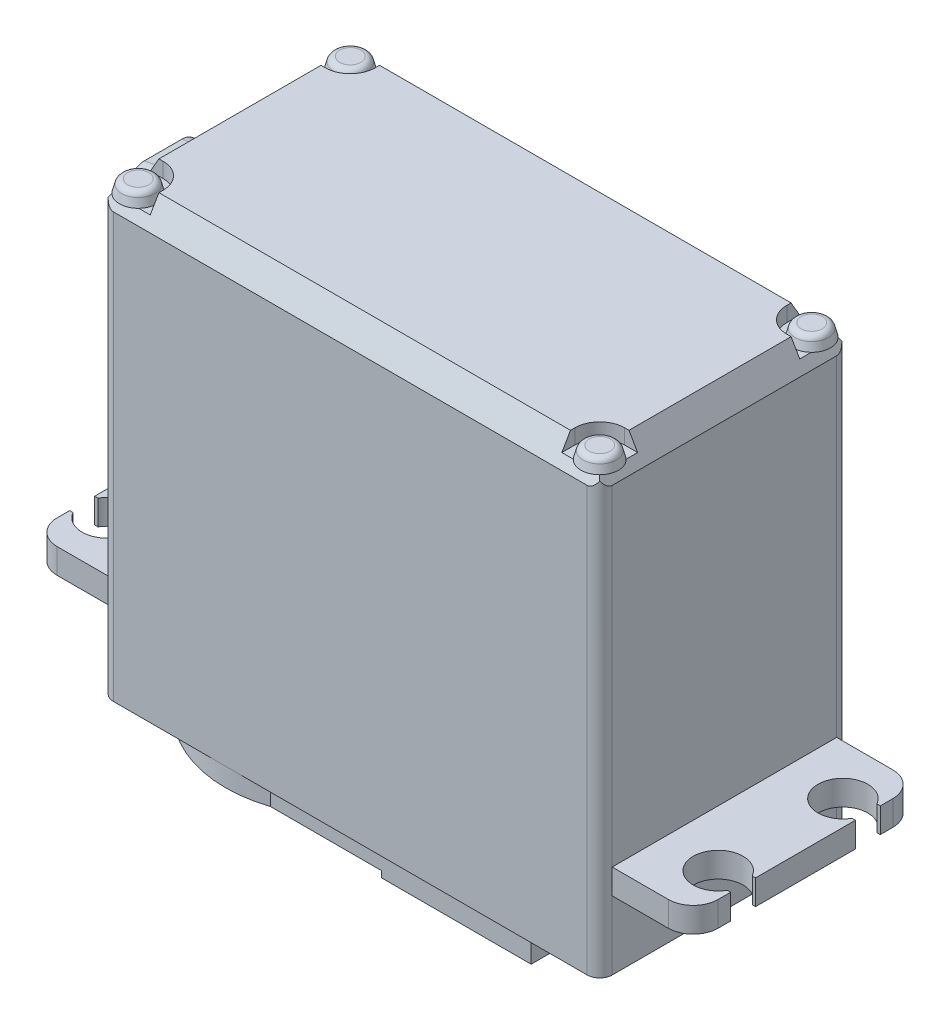
SolidWorks part; units mm, degrees
ref_plane "前视基准面" through (0, 0, 0) normal (0, 0, 1) x (1, 0, 0)
ref_plane "上视基准面" through (0, 0, 0) normal (0, 1, 0) x (1, 0, 0)
ref_plane "右视基准面" through (0, 0, 0) normal (1, 0, 0) x (0, 0, -1)
sketch "草图1" plane through (0, 0, 0) normal (0, 1, 0) x (1, 0, 0)
  line L1 (0, 0) -> (40, 0)
  line L2 (0, 0) -> (0, -20)
  line L3 (0, -20) -> (40, -20)
  line L4 (40, 0) -> (40, -20)
  point P4 (0, 0)
  dimension "D1" = 40
  dimension "D2" = 20
extrude "凸台-拉伸1" add sketch "草图1" along normal blind 28.5
sketch "草图3" plane through (0, 0, 0) normal (0, 1, 0) x (1, 0, 0)
  line L0 (0, 0) -> (0, -20) construction
  line L7 (-6.5, -1) -> (46.5, -1)
  line L8 (-6.5, -1) -> (-6.5, -19)
  line L9 (-6.5, -19) -> (46.5, -19)
  line L10 (46.5, -1) -> (46.5, -19)
  line L11 (-6.5, -10) -> (0, -10) construction
  line L12 (20, -1) -> (20, 0) construction
  line L13 (40, 0) -> (0, 0) construction
  line L14 (40, 0) -> (0, 0) construction
  point P2 (0, 0)
  point P15 (0, 0)
  dimension "D1" = 18
  dimension "D2" = 53
sketch "草图8" plane through (0, 0, 0) normal (0, 1, 0) x (1, 0, 0)
  line L0 (0, -10) -> (-4.5, -10) construction
  line L1 (0, 0) -> (0, -20) construction
  line L2 (0, -10) -> (40, -10) construction
  line L3 (40, -20) -> (40, 0) construction
  line L4 (40, -10) -> (44.5, -10) construction
  line L5 (44.5, -10) -> (44.5, -5) construction
  line L6 (44.5, -10) -> (44.5, -15) construction
  line L7 (-4.5, -10) -> (-4.5, -5) construction
  line L8 (-4.5, -10) -> (-4.5, -15) construction
  line L9 (-4.5, -5) -> (-9.5, -5) construction
  line L10 (-4.5, -15) -> (-9.5, -15) construction
  line L11 (-9.5, -5) -> (-9.5, -4) construction
  line L12 (-9.5, -5) -> (-9.5, -6) construction
  line L13 (-9.5, -15) -> (-9.5, -14) construction
  line L14 (-9.5, -15) -> (-9.5, -16) construction
  line L15 (44.5, -5) -> (49.5, -5) construction
  line L16 (49.5, -5) -> (49.5, -4) construction
  line L17 (49.5, -5) -> (49.5, -6) construction
  line L18 (44.5, -15) -> (49.5, -15) construction
  line L19 (49.5, -15) -> (49.5, -14) construction
  line L20 (49.5, -15) -> (49.5, -16) construction
  line L21 (-9.5, -6) -> (-6.2321, -6)
  line L22 (-9.5, -4) -> (-6.2321, -4)
  line L23 (-9.5, -14) -> (-6.2321, -14)
  line L24 (-9.5, -16) -> (-6.2321, -16)
  line L25 (49.5, -4) -> (46.2321, -4)
  line L26 (49.5, -6) -> (46.2321, -6)
  line L27 (49.5, -14) -> (46.2321, -14)
  line L28 (49.5, -16) -> (46.2321, -16)
  line L29 (49.5, -4) -> (49.5, -6)
  line L30 (49.5, -14) -> (49.5, -16)
  line L31 (-9.5, -4) -> (-9.5, -6)
  line L32 (-9.5, -14) -> (-9.5, -16)
  circle A0 centre (-4.5, -5) radius 2 construction
  circle A1 centre (-4.5, -15) radius 2 construction
  circle A2 centre (44.5, -5) radius 2 construction
  circle A3 centre (44.5, -15) radius 2 construction
  arc A4 (-6.2321, -4) -> (-6.2352, -5.9945) centre (-4.5, -5) cw
  arc A5 (-6.2321, -14) -> (-6.2598, -15.9504) centre (-4.5, -15) cw
  arc A6 (46.2321, -4) -> (46.2321, -6) centre (44.5, -5) ccw
  arc A7 (46.2321, -14) -> (46.2321, -16) centre (44.5, -15) ccw
  dimension "D2" = 4
  dimension "D3" = 4
  dimension "D4" = 4
  dimension "D5" = 4
  dimension "D1" = 49
  dimension "D6" = 10
  dimension "D7" = 10
  dimension "D8" = 1
  dimension "D9" = 1
  dimension "D10" = 1
  dimension "D11" = 1
  dimension "D12" = 1
  dimension "D13" = 1
  dimension "D14" = 1
  dimension "D15" = 1
  dimension "D16" = 5
  dimension "D17" = 5
  dimension "D18" = 5
  dimension "D19" = 5
sketch "草图7" plane through (0, 0, 0) normal (0, 1, 0) x (1, 0, 0)
  line L0 (0, -10) -> (10, -10)
  line L1 (0, 0) -> (0, -20) construction
  circle A0 centre (10, -10) radius 2.5
  dimension "D2" = 5
  dimension "D1" = 10
extrude "凸台-拉伸4" add sketch "草图7" against normal blind 6.9754 contours A0
extrude "凸台-拉伸5" add sketch "草图1<2>" against normal blind 7.5
sketch "草图1<2>" plane through (0, 0, 0) normal (0, 1, 0) x (1, 0, 0) same geometry as "草图1"
extrude "凸台-拉伸6" add sketch "草图3" against normal blind 2
extrude "切除-拉伸4" cut sketch "草图8" against normal mid plane 10 contours L25 A6 L26 L29 | L27 A7 L28 L30 | A4 L22 L31 L21 | A5 L23 L32 L24 region at (-5.6384, 0, 5) region at (-5.6384, 0, 15) region at (45.6384, 0, 5) region at (45.6384, 0, 15)
sketch "草图9" plane through (0, -7.5, 0) normal (0, -1, 0) x (1, 0, 0)
  line L0 (40, 10) -> (34, 10) construction
  line L1 (40, 20) -> (40, 0) construction
  line L2 (34, 19.5) -> (34, 0.5)
  line L3 (0, 20) -> (40, 20) construction
  line L4 (40, 0) -> (0, 0) construction
  line L5 (34, 19.5) -> (13.1225, 19.5)
  line L6 (34, 0.5) -> (13.1225, 0.5)
  line L7 (0, 0) -> (0, 20) construction
  circle A0 centre (10, 10) radius 10 construction
  arc A1 (13.1225, 19.5) -> (13.1225, 0.5) centre (10, 10) ccw
  dimension "D6" = 20
  dimension "D1" = 6
  dimension "D2" = 20
  dimension "D3" = 19
  dimension "D4" = 10
  dimension "D5" = 10
extrude "凸台-拉伸7" add sketch "草图9" along normal blind 1.5 contours A1 L6 L2 L5 region at (17.8154, -7.5, 10)
sketch "草图13" plane through (0, -7.5, 0) normal (0, -1, 0) x (1, 0, 0)
  line L0 (34, 0.5) -> (13.1225, 0.5) construction
  line L1 (34, 19.5) -> (22, 19.5)
  line L2 (34, 19.5) -> (34, 0.5)
  line L3 (34, 0.5) -> (22, 0.5)
  line L4 (22, 19.5) -> (22, 0.5)
  dimension "D1" = 12
extrude "凸台-拉伸8" add sketch "草图13" along normal blind 2
sketch "草图14" plane through (0, -7.5, 0) normal (0, -1, 0) x (1, 0, 0)
  line L0 (40, 19) -> (40, 1) construction
  line L1 (31, 10) -> (40, 10) construction
  line L2 (40, 20) -> (40, 0) construction
  circle A0 centre (31, 10) radius 6
  dimension "D2" = 12
  dimension "D1" = 9
extrude "凸台-拉伸9" add sketch "草图14" along normal blind 1.5 contours A0
ref_plane "基准面2" through (0, 0, 10) normal (0, 0, -1) x (-1, 0, 0)
sketch "草图15" plane through (0, 0, 10) normal (0, 0, -1) x (-1, 0, 0)
  line L1 (0, 28.5) -> (0, -7.5) construction
  line L2 (0, -3.2) -> (-40, -3.2)
  line L3 (-40, 28.5) -> (-40, -7.5) construction
  line L5 (-40, -3.2) -> (-46.5, -2)
  line L6 (-46.5, -2) -> (6.5, -2)
  line L7 (6.5, -2) -> (0, -3.2)
  dimension "D1" = 1.2
extrude "凸台-拉伸10" add sketch "草图15" along normal mid plane 0.5
sketch "草图16" plane through (0, 0, 0) normal (0, 0, 1) x (1, 0, 0)
  line L0 (0, 26.5) -> (1.1547, 28.5)
  line L1 (0, 28.5) -> (0, -7.5) construction
  line L2 (0, 28.5) -> (40, 28.5) construction
  line L3 (1.1547, 28.5) -> (38.8453, 28.5)
  line L4 (38.8453, 28.5) -> (40, 26.5)
  line L5 (40, 28.5) -> (40, -7.5) construction
  line L6 (40, 26.5) -> (45, 26.5)
  line L7 (45, 26.5) -> (45, 36.5)
  line L8 (45, 36.5) -> (-5, 36.5)
  line L9 (-5, 36.5) -> (-5, 26.5)
  line L10 (-5, 26.5) -> (0, 26.5)
  point P6 (-14.9929, 45.5019)
  dimension "D1" = 10
  dimension "D2" = 50
  dimension "D3" = 120
  dimension "D4" = 2
  dimension "D5" = 2
  dimension "D6" = 120
extrude "切除-拉伸5" cut sketch "草图16" against normal mid plane 100 contours L9 L10 L0 L3 L4 L6 L7 L8
sketch "草图18" plane through (0, 0, 0) normal (1, 0, 0) x (0, 0, -1)
  line L0 (-20, 26.5) -> (-18.8453, 28.5)
  line L1 (0, 28.5) -> (-20, 28.5) construction
  line L2 (-18.8453, 28.5) -> (-1.1547, 28.5)
  line L3 (-1.1547, 28.5) -> (0, 26.5)
  line L4 (0, 26.5) -> (15, 26.5)
  line L5 (15, 26.5) -> (15, 36.5)
  line L6 (15, 36.5) -> (-35, 36.5)
  line L7 (-35, 36.5) -> (-35, 26.5)
  line L8 (-35, 26.5) -> (-20, 26.5)
  dimension "D1" = 120
  dimension "D2" = 120
  dimension "D3" = 50
  dimension "D4" = 10
extrude "切除-拉伸6" cut sketch "草图18" against normal mid plane 100 contours L6 L7 L8 L0 L2 L3 L4 L5
sketch "草图22" plane through (0, 28.5, 0) normal (0, 1, 0) x (1, 0, 0)
  line L0 (0, 0) -> (0, -1.5)
  line L1 (0, -1) -> (0, -19) construction
  line L2 (0, -1.5) -> (1.5, -1.5)
  line L3 (3.5, -1.5) -> (3.5, 0.5)
  line L4 (3.5, 0.5) -> (-0.5, 0.5)
  line L5 (1.5, -3.5) -> (-0.5, -3.5)
  line L6 (-0.5, -3.5) -> (-0.5, 0.5)
  line L7 (19.8, -10) -> (-19.8, -10) construction
  line L8 (3.5, -18.5) -> (3.5, -20.5)
  line L9 (1.5, -16.5) -> (-0.5, -16.5)
  line L10 (-0.5, -16.5) -> (-0.5, -20.5)
  line L11 (3.5, -20.5) -> (-0.5, -20.5)
  line L12 (20, -1.1547) -> (20, -18.8453) construction
  line L13 (1.1547, -1.1547) -> (38.8453, -1.1547) construction
  line L14 (1.1547, -18.8453) -> (38.8453, -18.8453) construction
  line L15 (36.5, -18.5) -> (36.5, -20.5)
  line L16 (36.5, -20.5) -> (40.5, -20.5)
  line L17 (40.5, -16.5) -> (40.5, -20.5)
  line L18 (38.5, -16.5) -> (40.5, -16.5)
  line L19 (36.5, -1.5) -> (36.5, 0.5)
  line L20 (38.5, -3.5) -> (40.5, -3.5)
  line L21 (40.5, -3.5) -> (40.5, 0.5)
  line L22 (36.5, 0.5) -> (40.5, 0.5)
  circle A0 centre (1.5, -1.5) radius 2 construction
  arc A1 (3.5, -1.5) -> (1.3994, -3.4975) centre (1.5, -1.5) cw
  arc A2 (3.5, -18.5) -> (1.3994, -16.5025) centre (1.5, -18.5) ccw
  arc A3 (36.5, -18.5) -> (38.6006, -16.5025) centre (38.5, -18.5) cw
  arc A4 (36.5, -1.5) -> (38.6006, -3.4975) centre (38.5, -1.5) ccw
  point P13 (0.5, -3.5)
  point P20 (0.5, -16.5)
  line M8 (38.8453, -1.1547) -> (1.1547, -1.1547)
  line M9 (1.1547, -1.1547) -> (1.1547, -18.8453)
  line M10 (1.1547, -18.8453) -> (38.8453, -18.8453)
  line M11 (38.8453, -18.8453) -> (38.8453, -1.1547)
  dimension "D3" = 4
  dimension "D1" = 1.5
  dimension "D2" = 1.5
  dimension "D4" = 4
extrude "切除-拉伸11" cut sketch "草图22" against normal blind 1.2 contours L8 A2 L9 M9 M10 | A1 L3 L5 M8 M9 | L19 A4 L20 M11 M8 | A3 L15 L18 M10 M11 | L18 L15 L16 L17 M11 M10 | L22 L19 L20 L21 M8 M11 | L6 L5 L3 L4 | L11 L8 L9 L10 M10 M9 region at (2.1931, 28.5, 2.1931) region at (1.0666, 28.5, 1.0666) region at (37.8069, 28.5, 2.1931) region at (38.9334, 28.5, 1.0666) region at (1.0666, 28.5, 18.9334) region at (2.1931, 28.5, 17.8069) region at (37.8069, 28.5, 17.8069) region at (38.9334, 28.5, 18.9334)
sketch "草图24" plane through (0, 28.5, 0) normal (0, 1, 0) x (1, 0, 0)
  line L0 (0, 0) -> (1.5, 0)
  line L1 (0, 0) -> (40, 0) construction
  line L2 (1.5, 0) -> (1.5, -1.5)
  line L3 (40, 0) -> (38.5, 0)
  line L4 (38.5, 0) -> (38.5, -1.5)
  line L5 (40, -20) -> (38.5, -20)
  line L6 (0, -20) -> (40, -20) construction
  line L7 (38.5, -20) -> (38.5, -18.5)
  line L8 (0, -20) -> (1.5, -20)
  line L9 (1.5, -20) -> (1.5, -18.5)
  circle A0 centre (1.5, -1.5) radius 1.5
  circle A1 centre (38.5, -1.5) radius 1.5
  circle A2 centre (38.5, -18.5) radius 1.5
  circle A3 centre (1.5, -18.5) radius 1.5
  dimension "D1" = 1.5
  dimension "D2" = 1.5
  dimension "D3" = 1.5
  dimension "D4" = 1.5
  dimension "D5" = 1.5
  dimension "D6" = 1.5
  dimension "D7" = 1.5
  dimension "D8" = 1.5
sketch "草图25" plane through (0, 27.3, 0) normal (0, 1, 0) x (1, 0, 0)
  circle A0 centre (1.5, -1.5) radius 1.5
  circle A1 centre (38.5, -1.5) radius 1.5
  circle A2 centre (38.5, -18.5) radius 1.5
  circle A3 centre (1.5, -18.5) radius 1.5
extrude "凸台-拉伸12" add sketch "草图25" along normal blind 1 draft 15
sketch "草图29" plane through (0, -9, 0) normal (0, -1, 0) x (1, 0, 0)
  circle A0 centre (10, 10) radius 6.25
  dimension "D1" = 12.5
extrude "凸台-拉伸15" add sketch "草图29" along normal blind 1.2
sketch "草图30" plane through (0, -10.2, 0) normal (0, -1, 0) x (1, 0, 0)
  circle A0 centre (10, 10) radius 5
  dimension "D1" = 10
extrude "凸台-拉伸16" add sketch "草图30" along normal blind 0.3
sketch "草图31" plane through (0, -10.5, 0) normal (0, -1, 0) x (1, 0, 0)
  line L0 (10, 10) -> (13, 10) construction
  line L1 (10, 10) -> (12.9763, 10.376) construction
  line L2 (10, 10) -> (12.9057, 10.7461) construction
  line L3 (12.9763, 10.376) -> (12.4215, 10.6217)
  line L4 (12.9763, 10.376) -> (12.5, 10)
  line L5 (12.9763, 9.624) -> (12.5, 10)
  line L6 (12.9763, 9.624) -> (12.4215, 9.3783)
  line L7 (12.7893, 8.8956) -> (12.4215, 9.3783)
  line L8 (12.7893, 8.8956) -> (12.1908, 8.7956)
  line L9 (12.4271, 8.2366) -> (12.1908, 8.7956)
  line L10 (12.4271, 8.2366) -> (11.8224, 8.2886)
  line L11 (11.9123, 7.6885) -> (11.8224, 8.2886)
  line L12 (11.9123, 7.6885) -> (11.3396, 7.8892)
  line L13 (11.2773, 7.2855) -> (11.3396, 7.8892)
  line L14 (11.2773, 7.2855) -> (10.7725, 7.6224)
  line L15 (10.5621, 7.0531) -> (10.7725, 7.6224)
  line L16 (10.5621, 7.0531) -> (10.157, 7.5049)
  line L17 (9.8116, 7.0059) -> (10.157, 7.5049)
  line L18 (9.8116, 7.0059) -> (9.5315, 7.5443)
  line L19 (9.0729, 7.1468) -> (9.5315, 7.5443)
  line L20 (9.0729, 7.1468) -> (8.9356, 7.7379)
  line L21 (8.3925, 7.467) -> (8.9356, 7.7379)
  line L22 (8.3925, 7.467) -> (8.4064, 8.0737)
  line L23 (7.8131, 7.9464) -> (8.4064, 8.0737)
  line L24 (7.8131, 7.9464) -> (7.9775, 8.5305)
  line L25 (7.3711, 8.5547) -> (7.9775, 8.5305)
  line L26 (7.3711, 8.5547) -> (7.6756, 9.0797)
  line L27 (7.0943, 9.2539) -> (7.6756, 9.0797)
  line L28 (7.0943, 9.2539) -> (7.5197, 9.6867)
  line L29 (7, 10) -> (7.5197, 9.6867)
  line L30 (7, 10) -> (7.5197, 10.3133)
  line L31 (7.0943, 10.7461) -> (7.5197, 10.3133)
  line L32 (7.0943, 10.7461) -> (7.6756, 10.9203)
  line L33 (7.3711, 11.4453) -> (7.6756, 10.9203)
  line L34 (7.3711, 11.4453) -> (7.9775, 11.4695)
  line L35 (7.8131, 12.0536) -> (7.9775, 11.4695)
  line L36 (7.8131, 12.0536) -> (8.4064, 11.9263)
  line L37 (8.3925, 12.533) -> (8.4064, 11.9263)
  line L38 (8.3925, 12.533) -> (8.9356, 12.2621)
  line L39 (9.0729, 12.8532) -> (8.9356, 12.2621)
  line L40 (9.0729, 12.8532) -> (9.5315, 12.4557)
  line L41 (9.8116, 12.9941) -> (9.5315, 12.4557)
  line L42 (9.8116, 12.9941) -> (10.157, 12.4951)
  line L43 (10.5621, 12.9469) -> (10.157, 12.4951)
  line L44 (10.5621, 12.9469) -> (10.7725, 12.3776)
  line L45 (11.2773, 12.7145) -> (10.7725, 12.3776)
  line L46 (11.2773, 12.7145) -> (11.3396, 12.1108)
  line L47 (11.9123, 12.3115) -> (11.3396, 12.1108)
  line L48 (11.9123, 12.3115) -> (11.8224, 11.7114)
  line L49 (12.4271, 11.7634) -> (11.8224, 11.7114)
  line L50 (12.4271, 11.7634) -> (12.1908, 11.2044)
  line L51 (12.7893, 11.1044) -> (12.1908, 11.2044)
  line L52 (12.7893, 11.1044) -> (12.4215, 10.6217)
  circle A0 centre (10, 10) radius 3 construction
  circle A1 centre (10, 10) radius 2.5 construction
  point P83 (10, 10)
  dimension "D1" = 5
  dimension "D2" = 6
  dimension "D5" = 0.5
  dimension "D3" = 7.2
  dimension "D4" = 7.2
  dimension "D6" = 25
extrude "凸台-拉伸17" add sketch "草图31" along normal blind 3.5
sketch "草图33" plane through (0, -10.5, 0) normal (0, -1, 0) x (1, 0, 0)
  circle A0 centre (10, 10) radius 1.25
  dimension "D1" = 2.5
extrude "切除-拉伸12" cut sketch "草图33" along normal blind 10 contours A0
fillet "圆角1" radius 2 4 edges at (46.5, -1, 19) (46.5, -1, 1) (-6.5, -1, 1) (-6.5, -1, 19)
fillet "圆角2" radius 1 4 edges at (0, 9.5, 20) (40, 9.5, 20) (40, 9.5, 0) (0, 9.5, 0)
fillet "圆角4" radius 0.5 4 edges at (38.5, 28.3, 2.7321) (1.5, 28.3, 2.7321) (1.5, 28.3, 19.7321) (38.5, 28.3, 19.7321)
sketch "草图34" plane through (0, 0, 0) normal (-1, 0, 0) x (0, 0, 1)
  line L0 (10, 28.5) -> (10, 21.5) construction
  line L1 (16.5, 28.5) -> (3.5, 28.5) construction
  line L2 (10, 18.7) -> (10, -18.7) construction
  line L3 (10, 21.5) -> (6.5, 21.5) construction
  line L4 (6.5, 23.75) -> (13.5, 23.75)
  line L5 (6.5, 23.75) -> (6.5, 19.25)
  line L6 (6.5, 19.25) -> (13.5, 19.25)
  line L7 (13.5, 23.75) -> (13.5, 19.25)
  point P12 (10, 23.75)
  dimension "D1" = 7
  dimension "D2" = 7
  dimension "D3" = 4.5
extrude "凸台-拉伸18" add sketch "草图34" along normal blind 1 contours L4 L7 L6 L5
sketch "草图35" plane through (-1, 0, 0) normal (-1, 0, 0) x (0, 0, 1)
  line L0 (10, 23.5) -> (10, 21.5) construction
  line L1 (10, 18.7) -> (10, -18.7) construction
  line L2 (10, 21.5) -> (10, 19.5) construction
  line L3 (10, 21.5) -> (13.5, 21.5) construction
  line L4 (13.5, 23.75) -> (13.5, 19.25) construction
  line L5 (8.5, 23.5) -> (11.5, 23.5)
  line L6 (8.5, 19.5) -> (11.5, 19.5)
  circle A0 centre (11.5, 21.5) radius 2 construction
  arc A1 (11.5, 23.5) -> (11.5, 19.5) centre (11.5, 21.5) cw
  arc A2 (8.5, 23.5) -> (8.5, 19.5) centre (8.5, 21.5) ccw
  point P13 (0, 0)
  dimension "D4" = 3.5
  dimension "D1" = 2
  dimension "D2" = 2
  dimension "D3" = 1.5
extrude "凸台-拉伸19" add sketch "草图35" along normal blind 4 draft 10 contours L5 A1 L6 A2
